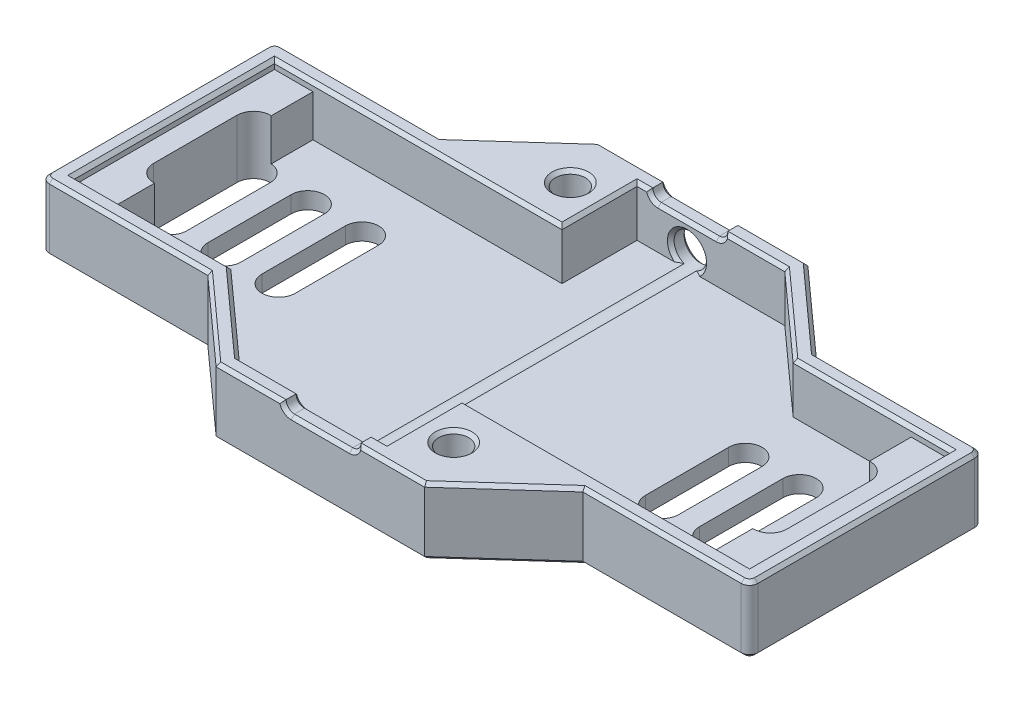
SolidWorks part; units mm, degrees
ref_plane "Front Plane" through (0, 0, 0) normal (0, 0, 1) x (1, 0, 0)
ref_plane "Top Plane" through (0, 0, 0) normal (0, 1, 0) x (1, 0, 0)
ref_plane "Right Plane" through (0, 0, 0) normal (1, 0, 0) x (0, 0, -1)
sketch "Sketch1" plane through (0, 0, 0) normal (0, 1, 0) x (1, 0, 0)
  line L2 (0, 61.021) -> (0, -61.021) construction
  line L4 (-42.5, 13) -> (-42.5, -13)
  line L6 (42.5, 13) -> (42.5, -13)
  line L7 (-64.4166, 0) -> (64.4166, 0) construction
  line L8 (-12.5, 23) -> (12.5, 23)
  line L9 (12.5, 23) -> (22.5, 14)
  line L11 (-22.5, -14) -> (-12.5, -23)
  line L12 (-12.5, -23) -> (12.5, -23)
  line L13 (12.5, -23) -> (22.5, -14)
  line L17 (22.5, 14) -> (41.5, 14)
  line L18 (41.5, -14) -> (22.5, -14)
  line L21 (-22.5, -14) -> (-41.5, -14)
  line L22 (-41.5, 14) -> (-22.5, 14)
  line L23 (-22.5, 14) -> (-12.5, 23)
  arc A0 (41.5, 14) -> (42.5, 13) centre (41.5, 13) cw
  arc A1 (41.5, -14) -> (42.5, -13) centre (41.5, -13) ccw
  arc A2 (-42.5, -13) -> (-41.5, -14) centre (-41.5, -13) ccw
  arc A3 (-41.5, 14) -> (-42.5, 13) centre (-41.5, 13) ccw
  point P0 (0, 0)
  point P1 (22.5, 14)
  point P2 (22.5, -14)
  point P3 (-22.5, -14)
  point P25 (0, 0)
  dimension "D3" = 1
  dimension "D4" = 23
  dimension "D1" = 45
  dimension "D2" = 25
  dimension "D5" = 85
  dimension "D6" = 28
sketch "Sketch3" [suppressed] plane through (0, 0, 0) normal (0, 1, 0) x (1, 0, 0)
  line L0 (0, 54.1428) -> (0, -67.8993) construction
  line L1 (-64.1281, 0) -> (64.7051, 0) construction
  line L2 (-12.5, 23) -> (12.5, 23)
  line L3 (12.5, 23) -> (22.5, 14)
  line L6 (-22.5, 14) -> (-12.5, 23)
  line L7 (-22.5, -14) -> (-12.5, -23)
  line L9 (-12.5, -23) -> (12.5, -23)
  line L10 (12.5, -23) -> (22.5, -14)
  line L11 (-22.5, 14) -> (-22.5, -14)
  line L12 (22.5, -14) -> (22.5, 14)
  dimension "D1" = 45
  dimension "D2" = 25
  dimension "D3" = 23
extrude "Boss-Extrude1" add sketch "Sketch1" along normal blind 7 and the other way blind 1
shell "Shell1" thickness 2 removed face at (0, 7, 0)
sketch "Sketch6" plane through (0, 0, 0) normal (0, 1, 0) x (1, 0, 0)
  line L0 (-21.7325, 12) -> (-6, 12)
  line L1 (-6, 12) -> (-6, 21)
  line L2 (11.7325, 21) -> (-11.7325, 21) construction
  line L3 (-6, 21) -> (-11.7325, 21)
  line L4 (-11.7325, 21) -> (-21.7325, 12)
  line L5 (11.7325, -21) -> (21.7325, -12)
  line L6 (21.7325, -12) -> (6, -12)
  line L7 (6, -12) -> (6, -21)
  line L8 (-11.7325, -21) -> (11.7325, -21) construction
  line L9 (6, -21) -> (11.7325, -21)
  dimension "D1" = 6
  dimension "D2" = 6
sketch "fastener screw holes" plane through (0, 0, 0) normal (0, 1, 0) x (1, 0, 0)
  line L0 (0, 38.3944) -> (0, -51.1968) construction
  line L1 (-52.5959, 0) -> (65.7321, 0) construction
  circle A0 centre (10, -17) radius 1.8
  circle A1 centre (-10, 17) radius 1.8
  point P4 (10, -17.0266)
  point P9 (-8.4114, 17.1303)
  dimension "D5" = 3.6
  dimension "D1" = 10
  dimension "D2" = 10
  dimension "D3" = 17
  dimension "D4" = 17
extrude "Boss-Extrude2" add sketch "Sketch6" along normal blind 7
extrude "Cut-Extrude1" cut sketch "fastener screw holes" along normal up to surface and the other way up to surface up to face at (0, 7, 0) other way up to face at (0, -1, 0)
sketch "cable exit hole" plane through (0, 0, 0) normal (0, 0, 1) x (1, 0, 0)
  circle A0 centre (0, 2.8) radius 1.95
  point P2 (0, 0)
  dimension "D2" = 3.9
  dimension "D1" = 2.8
extrude "Cut-Extrude2" cut sketch "cable exit hole" against normal up to surface and the other way up to surface contours A0 up to face at (0, 3, -23) other way up to face at (-2.8663, 4, 21)
sketch "Sketch7" plane through (0, 0, 0) normal (0, 0, 1) x (1, 0, 0)
  line L0 (0, 26.5192) -> (0, -25.5049) construction
  line L1 (-24.2779, 0) -> (28.8134, 0) construction
  line L6 (-3.5, 25) -> (3.5, 25)
  line L9 (-4.5, 24) -> (-4.5, 7)
  line L10 (-3.5, 6) -> (3.5, 6)
  line L11 (4.5, 24) -> (4.5, 7)
  arc A4 (3.5, 6) -> (4.5, 7) centre (3.5, 7) ccw
  arc A5 (-4.5, 7) -> (-3.5, 6) centre (-3.5, 7) ccw
  arc A6 (3.5, 25) -> (4.5, 24) centre (3.5, 24) cw
  arc A7 (-3.5, 25) -> (-4.5, 24) centre (-3.5, 24) ccw
  point P5 (0, 0)
  point P6 (0, 0)
  dimension "D1" = 1
  dimension "D2" = 9
  dimension "D3" = 19
  dimension "D4" = 6
extrude "Cut-Extrude3" cut sketch "Sketch7" against normal blind 27 and the other way blind 27
chamfer "Chamfer2" distance 0.4 angle 45 66 edges at (-32, -1, -14) (-42.2071, -1, -13.7071) (-42.5, -1, 0) (-42.2071, -1, 13.7071) (-32, -1, 14) (-17.5, -1, 18.5) (0, -1, 23) (17.5, -1, 18.5) (32, -1, 14) (42.2071, -1, 13.7071) (42.5, -1, 0) (42.2071, -1, -13.7071) (32, -1, -14) (17.5, -1, -18.5) (0, -1, -23) (-17.5, -1, -18.5) (10, -1, 15.2) (10, 7, 15.2) (-10, -1, -18.8) (-10, 7, -18.8) (0, 4.75, -21) (-1.95, 2.8, -23) (4.2071, 6.2929, -21) (-4.2071, 6.2929, -21) (0, 6, -21) (8.1163, 7, -21) (16.7325, 7, -16.5) (31.1163, 7, -12) (40.5, 7, 0) (5.25, 7, 21) (6, 7, 16.5) (23.25, 7, 12) (4.2071, 6.2929, 21) (0, 6, 21) (-5.25, 7, -21) (-6, 7, -16.5) (-23.25, 7, -12) (-40.5, 7, 0) (-4.2071, 6.2929, 21) (-8.1163, 7, 21) (-31.1163, 7, 12) (-16.7325, 7, 16.5) (-4.2071, 6.2929, 23) (4.2071, 6.2929, 23) (0, 6, 23) (-32, 7, -14) (-42.2071, 7, -13.7071) (-8.5, 7, 23) (-17.5, 7, 18.5) (-32, 7, 14) (-42.2071, 7, 13.7071) (-42.5, 7, 0) (-8.5, 7, -23) (-17.5, 7, -18.5) (4.2071, 6.2929, -23) (-4.2071, 6.2929, -23) (0, 6, -23) (32, 7, 14) (42.2071, 7, 13.7071) (8.5, 7, -23) (17.5, 7, -18.5) (32, 7, -14) (42.2071, 7, -13.7071) (42.5, 7, 0) (17.5, 7, 18.5) (8.5, 7, 23)
sketch "Sketch8" plane through (0, 0, 0) normal (0, 1, 0) x (1, 0, 0)
  line L0 (-40.9, 12.4) -> (-35.8851, 12.4)
  line L1 (-40.9, 12.4) -> (-6.4, 12.4) construction
  line L2 (-35.8851, 12.4) -> (-35.8851, -12.4)
  line L3 (-21.886, -12.4) -> (-40.9, -12.4) construction
  line L4 (-35.8851, -12.4) -> (-40.9, -12.4)
  line L5 (-40.9, -12.4) -> (-40.9, 12.4)
  line L6 (40.9, -12.4) -> (35.8946, -12.4)
  line L7 (40.9, -12.4) -> (6.4, -12.4) construction
  line L8 (35.8946, -12.4) -> (35.8946, 12.4)
  line L9 (21.886, 12.4) -> (40.9, 12.4) construction
  line L10 (35.8946, 12.4) -> (40.9, 12.4)
  line L11 (40.9, 12.4) -> (40.9, -12.4)
extrude "Boss-Extrude3" add sketch "Sketch8" along normal blind 6
sketch "Sketch10" plane through (0, 0, 0) normal (0, 1, 0) x (1, 0, 0)
  line L0 (0, 27.422) -> (0, -31.3035) construction
  line L1 (-47.728, 0) -> (55.5628, 0) construction
  line L2 (-36, -5) -> (-36, 5) construction
  line L3 (-38, -5) -> (-38, 5)
  line L4 (-34, -5) -> (-34, 5)
  line L5 (-29.5, -5) -> (-29.5, 5) construction
  line L6 (-31.5, -5) -> (-31.5, 5)
  line L7 (-27.5, -5) -> (-27.5, 5)
  line L8 (-23, -5) -> (-23, 5) construction
  line L9 (-25, -5) -> (-25, 5)
  line L10 (-21, -5) -> (-21, 5)
  line L11 (23, -5) -> (23, 5) construction
  line L12 (21, -5) -> (21, 5)
  line L13 (25, -5) -> (25, 5)
  line L14 (29.5, -5) -> (29.5, 5) construction
  line L15 (27.5, -5) -> (27.5, 5)
  line L16 (31.5, -5) -> (31.5, 5)
  line L17 (36, -5) -> (36, 5) construction
  line L18 (34, -5) -> (34, 5)
  line L19 (38, -5) -> (38, 5)
  arc A0 (-38, -5) -> (-34, -5) centre (-36, -5) ccw
  arc A1 (-34, 5) -> (-38, 5) centre (-36, 5) ccw
  arc A2 (-31.5, -5) -> (-27.5, -5) centre (-29.5, -5) ccw
  arc A3 (-27.5, 5) -> (-31.5, 5) centre (-29.5, 5) ccw
  arc A4 (-25, -5) -> (-21, -5) centre (-23, -5) ccw
  arc A5 (-21, 5) -> (-25, 5) centre (-23, 5) ccw
  arc A6 (21, -5) -> (25, -5) centre (23, -5) ccw
  arc A7 (25, 5) -> (21, 5) centre (23, 5) ccw
  arc A8 (27.5, -5) -> (31.5, -5) centre (29.5, -5) ccw
  arc A9 (31.5, 5) -> (27.5, 5) centre (29.5, 5) ccw
  arc A10 (34, -5) -> (38, -5) centre (36, -5) ccw
  arc A11 (38, 5) -> (34, 5) centre (36, 5) ccw
  point P7 (-36, 0)
  point P13 (-29.5, 0)
  point P20 (-23, 0)
  point P27 (23, 0)
  point P34 (29.5, 0)
  point P41 (36, 0)
  point P47 (0, 0)
  point P48 (0, 0)
  point P49 (0, 0)
  dimension "D2" = 2
  dimension "D1" = 10
  dimension "D3" = 6.5
  dimension "D4" = 6.5
extrude "Cut-Extrude5" cut sketch "Sketch10" against normal blind 7 and the other way blind 7
